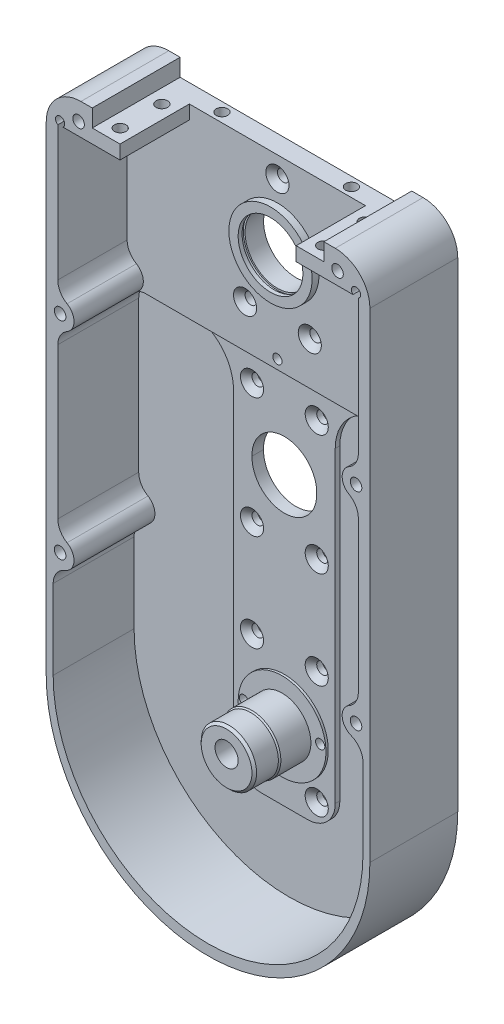
SolidWorks part; units mm, degrees
material "2014 Alloy"
ref_plane "Front" through (0, 0, 0) normal (0, 0, 1) x (1, 0, 0)
ref_plane "Top" through (0, 0, 0) normal (0, 1, 0) x (1, 0, 0)
ref_plane "Right" through (0, 0, 0) normal (1, 0, 0) x (0, 0, -1)
ref_plane "Plane1" through (0, 0, 38) normal (0, 0, 1) x (1, 0, 0)
sketch "Sketch1" plane through (0, 0, 38) normal (0, 0, 1) x (1, 0, 0)
  line L0 (70, 36) -> (-70, 36)
  line L1 (-70, 36) -> (-70, -179.1)
  line L2 (70, -179.1) -> (70, 36)
  arc A0 (-70, -179.1) -> (70, -179.1) centre (0, -179.1) ccw
  dimension "D2" = 70
  dimension "D1" = 215.1
  dimension "D3" = 36
extrude "Boss-Extrude1" add sketch "Sketch1" against normal blind 38
sketch "Sketch2" plane through (0, 0, 38) normal (0, 0, 1) x (1, 0, 0)
  line L0 (-38.1, 36) -> (-38.1, 30)
  line L1 (-38.1, 30) -> (-65, 30)
  line L2 (-65, 30) -> (-65, -34.5839)
  line L3 (-65, -52.6244) -> (-65, -124.0839)
  line L4 (-67, -143.0767) -> (-67, -177.5)
  line L5 (67, -177.5) -> (67, -143.0767)
  line L6 (65, -124.0839) -> (65, -52.6244)
  line L7 (65, -34.5839) -> (65, 30)
  line L8 (65, 30) -> (38.1, 30)
  line L9 (38.1, 30) -> (38.1, 36)
  line L10 (38.1, 36) -> (-38.1, 36)
  arc A0 (-65, -34.5839) -> (-61, -45.6962) centre (-64, -40.5) cw
  arc A1 (-61, -45.6962) -> (-65, -52.6244) centre (-57, -52.6244) ccw
  arc A2 (-65, -124.0839) -> (-61.8571, -135.6043) centre (-64, -130) cw
  arc A3 (-61.8571, -135.6043) -> (-67, -143.0767) centre (-59, -143.0767) ccw
  arc A4 (-67, -177.5) -> (67, -177.5) centre (0, -177.5) ccw
  arc A5 (67, -143.0767) -> (61.8571, -135.6043) centre (59, -143.0767) ccw
  arc A6 (61.8571, -135.6043) -> (65, -124.0839) centre (64, -130) cw
  arc A7 (65, -52.6244) -> (61, -45.6962) centre (57, -52.6244) ccw
  arc A8 (61, -45.6962) -> (65, -34.5839) centre (64, -40.5) cw
extrude "Cut-Extrude1" cut sketch "Sketch2" against normal blind 30
sketch "Sketch3" plane through (0, 0, 8) normal (0, 0, 1) x (1, 0, 0)
  line L0 (56.9289, -44.5) -> (-56.9289, -44.5)
  line L1 (-65, -52.6244) -> (-65, -124.0839)
  line L2 (-67, -143.0767) -> (-67, -177.5)
  line L3 (67, -177.5) -> (67, -143.0767)
  line L4 (65, -124.0839) -> (65, -52.6244)
  arc A0 (-56.9289, -44.5) -> (-60.8573, -45.6111) centre (-56.9289, -52) ccw
  arc A1 (-60.8573, -45.6111) -> (-61, -45.6962) centre (-64, -40.5) cw
  arc A2 (-61, -45.6962) -> (-65, -52.6244) centre (-57, -52.6244) ccw
  arc A3 (-65, -124.0839) -> (-61.8571, -135.6043) centre (-64, -130) cw
  arc A4 (-61.8571, -135.6043) -> (-67, -143.0767) centre (-59, -143.0767) ccw
  arc A5 (-67, -177.5) -> (67, -177.5) centre (0, -177.5) ccw
  arc A6 (67, -143.0767) -> (61.8571, -135.6043) centre (59, -143.0767) ccw
  arc A7 (61.8571, -135.6043) -> (65, -124.0839) centre (64, -130) cw
  arc A8 (65, -52.6244) -> (61, -45.6962) centre (57, -52.6244) ccw
  arc A9 (61, -45.6962) -> (60.8573, -45.6111) centre (64, -40.5) cw
  arc A10 (60.8573, -45.6111) -> (56.9289, -44.5) centre (56.9289, -52) ccw
extrude "Cut-Extrude2" cut sketch "Sketch3" against normal blind 5
sketch "Sketch4" plane through (0, 36, 0) normal (0, 1, 0) x (-1, 0, 0)
  line L0 (-70, 38) -> (-50.1, 38)
  line L1 (-50.1, 38) -> (-50.1, 0)
  line L2 (-50.1, 0) -> (-70, 0)
  line L3 (-70, 0) -> (-70, 38)
extrude "Boss-Extrude2" add sketch "Sketch4" along normal blind 7.5
sketch "Sketch5" plane through (0, 36, 0) normal (0, 1, 0) x (-1, 0, 0)
  line L0 (50.1, 38) -> (70, 38)
  line L1 (70, 38) -> (70, 0)
  line L2 (70, 0) -> (50.1, 0)
  line L3 (50.1, 0) -> (50.1, 38)
extrude "Boss-Extrude3" add sketch "Sketch5" along normal blind 7.5
sketch "Sketch6" plane through (0, 0, 38) normal (0, 0, 1) x (1, 0, 0)
  line L0 (-65, 30) -> (-62.6771, 30)
  line L1 (-65, 29.7679) -> (-65, 30)
  arc A0 (-62.6771, 30) -> (-65, 29.7679) centre (-64, 31.5) ccw
extrude "Cut-Extrude3" cut sketch "Sketch6" against normal blind 30
sketch "Sketch7" plane through (0, 0, 38) normal (0, 0, 1) x (1, 0, 0)
  line L0 (65, 30) -> (65, 29.7679)
  line L1 (62.6771, 30) -> (65, 30)
  arc A0 (65, 29.7679) -> (62.6771, 30) centre (64, 31.5) ccw
extrude "Cut-Extrude4" cut sketch "Sketch7" against normal blind 30
sketch "Sketch8" plane through (0, 0, 3) normal (0, 0, 1) x (1, 0, 0)
  line L0 (-22, -209.5) -> (-22, -44.5)
  line L1 (-22, -44.5) -> (22, -44.5)
  line L2 (22, -44.5) -> (22, -209.5)
  line L3 (22, -209.5) -> (-22, -209.5)
  point P7 (0, -209.5)
  dimension "D1" = 165
  dimension "D2" = 44
  dimension "D3" = 44.5
extrude "Boss-Extrude4" add sketch "Sketch8" along normal blind 2
ref_plane "Plane2" through (0, 0, 0) normal (0, -1, 0) x (1, 0, 0)
sketch "Sketch9" plane through (0, 0, 0) normal (0, -1, 0) x (1, 0, 0)
  line L0 (18, 11) -> (0, 11)
  line L1 (0, 11) -> (0, 8)
  line L2 (0, 8) -> (18, 8)
  line L3 (18, 8) -> (18, 11)
  line L4 (0, 11) -> (0, 8) construction
revolve "Revolve1" add sketch "Sketch9" angle 360 about L4 reverse direction yes
ref_plane "Plane3" through (0, -177.5, 0) normal (0, -1, 0) x (1, 0, 0)
ref_plane "Plane6" through (0, -179.1, 0) normal (0, 1, 0) x (0, 0, 1)
sketch "Sketch10" plane through (0, -179.1, 0) normal (0, -1, 0) x (1, 0, 0)
  line L0 (11.98, 30) -> (0, 30)
  line L1 (0, 30) -> (0, 5)
  line L2 (0, 5) -> (19, 5)
  line L3 (19, 5) -> (19, 6)
  line L4 (19, 6) -> (12.48, 6)
  line L5 (12.48, 6) -> (12.48, 19)
  line L6 (12.48, 19) -> (11.98, 19.5752)
  line L7 (11.98, 19.5752) -> (11.98, 30)
  line L8 (0, 30) -> (0, 5) construction
revolve "Revolve2" add sketch "Sketch10" angle 360 about L8 reverse direction yes
sketch "Sketch11" plane through (0, 0, 0) normal (0, -1, 0) x (1, 0, 0)
  line L0 (14, 11) -> (0, 11)
  line L1 (0, 11) -> (0, 0)
  line L2 (0, 0) -> (14, 0)
  line L3 (14, 0) -> (14, 8)
  line L4 (14, 8) -> (14.75, 8)
  line L5 (14.75, 8) -> (14.75, 9.3)
  line L6 (14.75, 9.3) -> (14, 9.3)
  line L7 (14, 9.3) -> (14, 11)
  line L8 (0, 11) -> (0, 0) construction
revolve "Cut-Revolve1" cut sketch "Sketch11" angle 360 about L8 reverse direction yes
hole_wizard "Ø4.0 (4) Diameter Hole1" positions "Sketch13" profile "Sketch12" hole size "Ø4.0" standard "ANSI Metric"
sketch "Sketch13" plane through (0, 0, 0) normal (0, 0, -1) x (-1, 0, 0)
  point P0 (-16.5, -177.5)
  point P1 (16.5, -177.5)
sketch "Sketch12" plane through (16.5, -177.5, 0) normal (1, 0, 0) x (0, 1, 0)
  line L0 (0, 0) -> (0, 38)
  line L1 (0, 38) -> (2, 38)
  line L2 (2, 38) -> (2, 0)
  line L5 (2, 0) -> (0, 0)
  line L11 (0, -6.35) -> (0, 107.95) construction
  dimension "Thru Hole Dia." = 4
  dimension "Thru Hole Depth" = 38
hole_wizard "Ø4.0 (4) Diameter Hole2" positions "Sketch15" profile "Sketch14" hole size "Ø4.0" standard "ANSI Metric"
sketch "Sketch15" plane through (0, 0, 0) normal (0, 0, -1) x (-1, 0, 0)
  point P0 (0, -40.5)
sketch "Sketch14" plane through (0, -40.5, 0) normal (1, 0, 0) x (0, 1, 0)
  line L0 (0, 0) -> (0, 38)
  line L1 (0, 38) -> (2, 38)
  line L2 (2, 38) -> (2, 0)
  line L5 (2, 0) -> (0, 0)
  line L11 (0, -6.35) -> (0, 107.95) construction
  dimension "Thru Hole Dia." = 4
  dimension "Thru Hole Depth" = 38
hole_wizard "Ø5.0 (5) Diameter Hole1" positions "Sketch17" profile "Sketch16" hole size "Ø5.0" standard "ANSI Metric"
sketch "Sketch17" plane through (0, 0, 8) normal (0, 0, 1) x (1, 0, 0)
  point P0 (14, -26)
  point P1 (-14, -26)
  point P2 (0, 27)
sketch "Sketch16" plane through (14, -26, 8) normal (1, 0, 0) x (0, -1, 0)
  line L0 (0, 0) -> (0, 8)
  line L1 (0, 8) -> (2.5, 8)
  line L2 (2.5, 8) -> (2.5, 0)
  line L5 (2.5, 0) -> (0, 0)
  line L11 (0, -6.35) -> (0, 107.95) construction
  dimension "Thru Hole Dia." = 5
  dimension "Thru Hole Depth" = 8
hole_wizard "M24 Clearance Hole1" positions "Sketch19" profile "Sketch18" hole size "M24" standard "ANSI Metric" end condition through all
sketch "Sketch19" plane through (0, 0, 5) normal (0, 0, 1) x (1, 0, 0)
  point P0 (0, -85)
sketch "Sketch18" plane through (0, -85, 5) normal (1, 0, 0) x (0, -1, 0)
  line L0 (0, 0) -> (0, 5)
  line L1 (0, 5) -> (14, 5)
  line L2 (14, 5) -> (14, 0)
  line L5 (14, 0) -> (0, 0)
  line L11 (0, -6.35) -> (0, 107.95) construction
  dimension "Thru Hole Dia." = 28
  dimension "Thru Hole Depth" = 5
hole_wizard "Ø10.0 (10) Diameter Hole1" positions "Sketch21" profile "Sketch20" hole size "Ø10.0" standard "ANSI Metric"
sketch "Sketch21" plane through (0, 0, 0) normal (0, 0, -1) x (-1, 0, 0)
  point P0 (0, -177.5)
sketch "Sketch20" plane through (0, -177.5, 0) normal (1, 0, 0) x (0, 1, 0)
  line L0 (0, 0) -> (0, 38)
  line L1 (0, 38) -> (5, 38)
  line L2 (5, 38) -> (5, 0)
  line L5 (5, 0) -> (0, 0)
  line L11 (0, -6.35) -> (0, 107.95) construction
  dimension "Thru Hole Dia." = 10
  dimension "Thru Hole Depth" = 38
hole_wizard "Ø5.0 (5) Diameter Hole2" positions "Sketch23" profile "Sketch22" hole size "Ø5.0" standard "ANSI Metric"
sketch "Sketch23" plane through (0, 0, 5) normal (0, 0, 1) x (1, 0, 0)
  point P0 (14, -201)
  point P1 (-14, -201)
  point P2 (-14, -152)
  point P3 (14, -152)
  point P4 (-14, -110)
  point P5 (14, -110)
  point P6 (-14, -58)
  point P7 (14, -58)
sketch "Sketch22" plane through (14, -201, 5) normal (1, 0, 0) x (0, -1, 0)
  line L0 (0, 0) -> (0, 5)
  line L1 (0, 5) -> (2.5, 5)
  line L2 (2.5, 5) -> (2.5, 2.5)
  line L3 (2.5, 2.5) -> (5, 0)
  line L5 (5, 0) -> (0, 0)
  line L6 (-2.5, 2.5) -> (-5, 0) construction
  line L11 (0, -6.35) -> (0, 107.95) construction
  dimension "Thru Hole Dia." = 5
  dimension "Thru Hole Depth" = 5
  dimension "Near C'Sink Dia." = 10
  dimension "Near C'Sink Angle" = 90
hole_wizard "Ø5.0 (5) Diameter Hole3" positions "Sketch25" profile "Sketch24" hole size "Ø5.0" standard "ANSI Metric"
sketch "Sketch25" plane through (0, 36, 0) normal (0, 1, 0) x (1, 0, 0)
  point P0 (44, -14)
  point P1 (44, -32)
  point P2 (-44, -32)
  point P3 (-44, -14)
sketch "Sketch24" plane through (44, 36, 14) normal (1, 0, 0) x (0, 0, 1)
  line L0 (0, 0) -> (0, 6)
  line L1 (0, 6) -> (2.5, 6)
  line L2 (2.5, 6) -> (2.5, 0)
  line L5 (2.5, 0) -> (0, 0)
  line L11 (0, -6.35) -> (0, 107.95) construction
  dimension "Thru Hole Dia." = 5
  dimension "Thru Hole Depth" = 6
hole_wizard "Ø5.0 (5) Diameter Hole4" positions "Sketch27" profile "Sketch26" hole size "Ø5.0" standard "ANSI Metric"
sketch "Sketch27" plane through (0, 36, 0) normal (0, 1, 0) x (1, 0, 0)
  point P0 (28, -4)
  point P1 (-28, -4)
sketch "Sketch26" plane through (28, 36, 4) normal (1, 0, 0) x (0, 0, 1)
  line L0 (0, 0) -> (0, 20)
  line L1 (0, 20) -> (2.5, 20)
  line L2 (2.5, 20) -> (2.5, 0)
  line L5 (2.5, 0) -> (0, 0)
  line L10 (0, 20) -> (-2.5, 20) construction
  line L11 (0, -6.35) -> (0, 107.95) construction
  dimension "Hole Dia." = 5
  dimension "Hole Depth" = 20
  dimension "Drill Angle" = 180
hole_wizard "Ø5.0 (5) Diameter Hole5" positions "Sketch29" profile "Sketch28" hole size "Ø5.0" standard "ANSI Metric"
sketch "Sketch29" plane through (0, 0, 38) normal (0, 0, 1) x (1, 0, 0)
  point P0 (64, -130)
  point P1 (-64, -130)
sketch "Sketch28" plane through (64, -130, 38) normal (1, 0, 0) x (0, -1, 0)
  line L0 (0, 0) -> (0, 35)
  line L1 (0, 35) -> (2.5, 35)
  line L2 (2.5, 35) -> (2.5, 0)
  line L5 (2.5, 0) -> (0, 0)
  line L10 (0, 35) -> (-2.5, 35) construction
  line L11 (0, -6.35) -> (0, 107.95) construction
  dimension "Hole Dia." = 5
  dimension "Hole Depth" = 35
  dimension "Drill Angle" = 180
hole_wizard "Ø5.0 (5) Diameter Hole6" positions "Sketch31" profile "Sketch30" hole size "Ø5.0" standard "ANSI Metric"
sketch "Sketch31" plane through (0, 0, 38) normal (0, 0, 1) x (1, 0, 0)
  point P0 (-56, 35.5)
  point P1 (56, 35.5)
  point P2 (64, -40.5)
  point P3 (-64, -40.5)
sketch "Sketch30" plane through (-56, 35.5, 38) normal (1, 0, 0) x (0, -1, 0)
  line L0 (0, 0) -> (0, 30)
  line L1 (0, 30) -> (2.5, 30)
  line L2 (2.5, 30) -> (2.5, 0)
  line L5 (2.5, 0) -> (0, 0)
  line L10 (0, 30) -> (-2.5, 30) construction
  line L11 (0, -6.35) -> (0, 107.95) construction
  dimension "Hole Dia." = 5
  dimension "Hole Depth" = 30
  dimension "Drill Angle" = 180
chamfer "Chamfer1" distance 2.5 angle 45 3 edges at (16.5, -26, 8) (-11.5, -26, 8) (2.5, 27, 8) first distance on face at (16.5, -26, 8)
chamfer "Chamfer2" distance 1 angle 45 1 edges at (-11.98, -179.1, 30)
fillet "Fillet1" radius 8 4 edges at (-65, -34.5839, 23) (65, -124.0839, 20.5) (65, -34.5839, 23) (-65, -124.0839, 20.5) tangent propagation no
fillet "Fillet2" radius 12 2 edges at (22, -209.5, 4) (-22, -209.5, 4) tangent propagation no
fillet "Fillet3" radius 15 2 edges at (-70, 43.5, 19) (70, 43.5, 19) tangent propagation no
fillet "Fillet4" radius 20 2 edges at (-22, -44.5, 4) (22, -44.5, 4) tangent propagation no
ref_plane "Plane4" through (0, -85, 0) normal (0, 1, 0) x (0, 0, 1)
ref_axis "Axis1" through (0, -85, -80.9) along (0, 0, 1)
ref_plane "Plane5" through (0, -85.75, 0) normal (0, 1, 0) x (0, 0, 1)
ref_axis "Axis2" through (0, -85.75, -80.9) along (0, 0, 1)
sketch "Sketch32" plane through (0, 0, 5) normal (0, 0, 1) x (1, 0, 0)
  circle A0 centre (0, -85.75) radius 14
  dimension "D1" = 28
extrude "Cut-Extrude5" cut sketch "Sketch32" against normal through all
